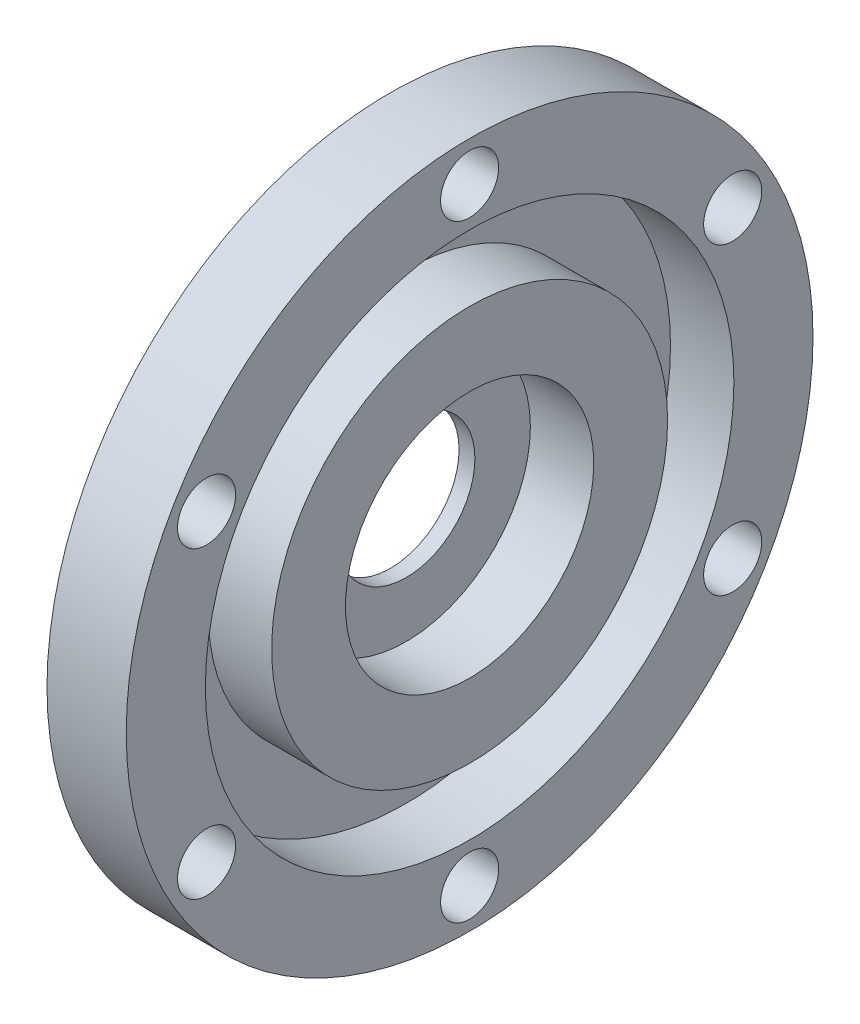
SolidWorks part; units mm, degrees
ref_plane "Front Plane" through (0, 0, 0) normal (0, 0, 1) x (1, 0, 0)
ref_plane "Top Plane" through (0, 0, 0) normal (0, 1, 0) x (1, 0, 0)
ref_plane "Right Plane" through (0, 0, 0) normal (1, 0, 0) x (0, 0, -1)
sketch "Sketch1" plane through (0, 0, 0) normal (1, 0, 0) x (0, 0, -1)
  circle A0 centre (0, 0) radius 13
  circle A1 centre (0, 0) radius 23.5
  circle A2 centre (0, 0) radius 50.025
  circle A3 centre (0, 0) radius 65
  circle A4 centre (0, 57.5) radius 2.5
  circle A5 centre (0, 0) radius 57.5 construction
  circle A6 centre (49.7965, 28.75) radius 2.5
  circle A7 centre (49.7965, -28.75) radius 2.5
  circle A8 centre (0, -57.5) radius 2.5
  circle A9 centre (-49.7965, -28.75) radius 2.5
  circle A10 centre (-49.7965, 28.75) radius 2.5
  circle A11 centre (0, 0) radius 37.475
  point P22 (0, 0)
  dimension "D1" = 26
  dimension "D2" = 47
  dimension "D3" = 100.05
  dimension "D4" = 130
  dimension "D5" = 115
  dimension "D6" = 5
  dimension "D8" = 74.95
  dimension "D7" = 6
extrude "layer_extrude" add sketch "Sketch1" along normal blind 3 contours A3 A10 A9 A8 A7 A6 A4 A2 | A2 A1 | A1 A0 | A11 A1 region at (0, 0, 22.8353) region at (0, 0, 48.6101) region at (0, 0, 63.1615) region at (0, 0, 36.415)
extrude "bearing_support_extrude" add sketch "Sketch1<3>" along normal blind 15 contours A11 A1 | A3 A10 A9 A8 A7 A6 A4 A2 region at (0, 0, 63.1615) region at (0, 0, 36.415)
sketch "Sketch1<3>" plane through (0, 0, 0) normal (1, 0, 0) x (0, 0, -1) same geometry as "Sketch1"
sketch "Sketch2" plane through (15, 0, 0) normal (1, 0, 0) x (0, 0, -1)
  circle A0 centre (0, 57.5) radius 5.5
  circle A1 centre (49.7965, 28.75) radius 5.5
  circle A2 centre (49.7965, -28.75) radius 5.5
  circle A3 centre (0, -57.5) radius 5.5
  circle A4 centre (-49.7965, -28.75) radius 5.5
  circle A5 centre (-49.7965, 28.75) radius 5.5
  dimension "D1" = 11
extrude "Cut-Extrude1" cut sketch "Sketch2" against normal blind 8
